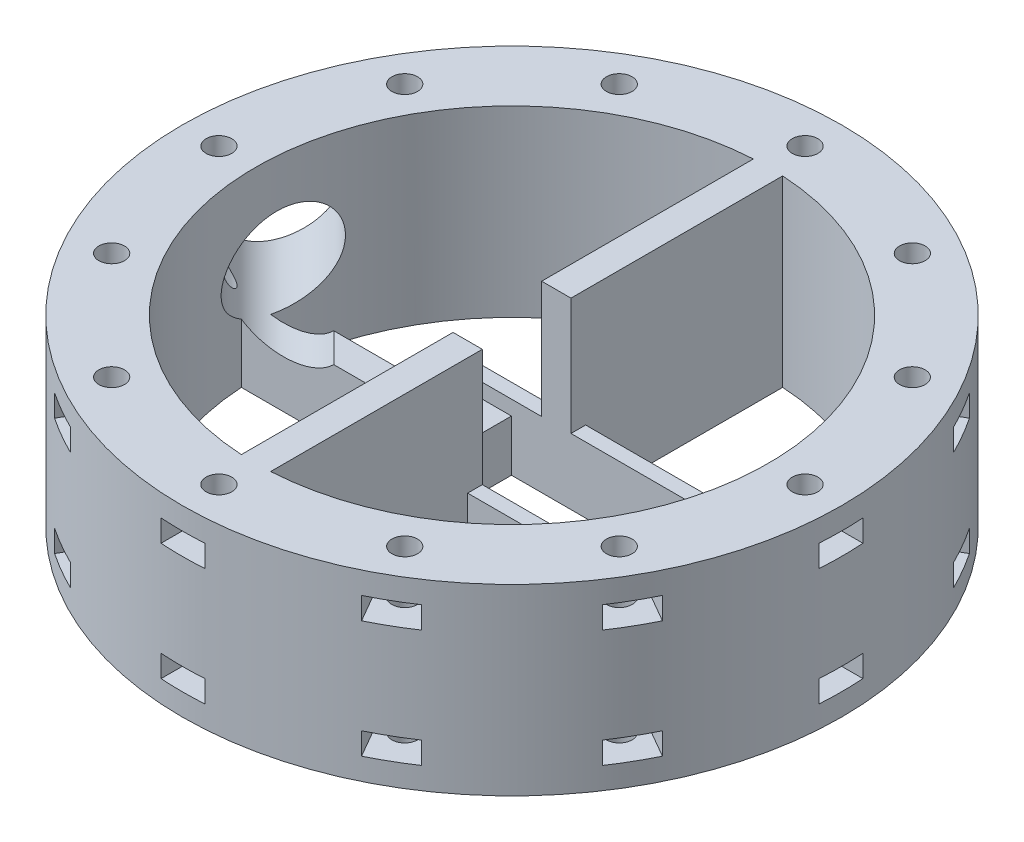
SolidWorks part; units mm, degrees
ref_plane "Front Plane" through (0, 0, 0) normal (0, 0, 1) x (1, 0, 0)
ref_plane "Top Plane" through (0, 0, 0) normal (0, 1, 0) x (1, 0, 0)
ref_plane "Right Plane" through (0, 0, 0) normal (1, 0, 0) x (0, 0, -1)
sketch "Sketch2" plane through (0, 0, 0) normal (0, 1, 0) x (1, 0, 0)
  line L0 (0, 0) -> (0, 45) construction
  circle A0 centre (0, 0) radius 45
  dimension "D1" = 90
extrude "Boss-Extrude1" add sketch "Sketch2" along normal blind 9
sketch "Sketch3" plane through (0, 9, 0) normal (0, 1, 0) x (1, 0, 0)
  line L0 (0, 45) -> (0, 0) construction
  line L1 (0, 0) -> (45, 0) construction
  line L2 (-10.95, 6.05) -> (21.3, 6.05)
  line L3 (21.3, 6.05) -> (21.3, -6.05)
  line L4 (-10.95, 6.05) -> (-10.95, -6.05)
  line L5 (-10.95, -6.05) -> (21.3, -6.05)
  circle A0 centre (0, 0) radius 45 construction
  point P12 (21.3, 0)
  point P13 (-10.95, 0)
  dimension "D1" = 32.25
  dimension "D2" = 10.95
  dimension "D3" = 12.1
extrude "Cut-Extrude1" cut sketch "Sketch3" against normal blind 2
sketch "Sketch4" plane through (0, 7, 0) normal (0, 1, 0) x (1, 0, 0)
  line L0 (5.175, 6.05) -> (5.175, -6.05) construction
  line L1 (21.3, 6.05) -> (-10.95, 6.05) construction
  line L2 (-10.95, -6.05) -> (21.3, -6.05) construction
  line L4 (-6.125, 6.05) -> (16.475, 6.05)
  line L5 (-6.125, 6.05) -> (-6.125, -6.05)
  line L6 (-6.125, -6.05) -> (16.475, -6.05)
  line L7 (16.475, 6.05) -> (16.475, -6.05)
  line L8 (-6.125, 6.05) -> (16.475, -6.05) construction
  line L9 (-6.125, -6.05) -> (16.475, 6.05) construction
  point P6 (5.175, 0)
  dimension "D1" = 22.6
extrude "Cut-Extrude2" cut sketch "Sketch4" against normal through all
sketch "Sketch6" plane through (0, 7, 0) normal (0, 1, 0) x (1, 0, 0)
  line L0 (-10.95, 0) -> (21.3, 0) construction
  line L1 (-10.95, 6.05) -> (-10.95, -6.05) construction
  line L2 (21.3, -6.05) -> (21.3, 6.05) construction
  line L3 (5.175, 6.05) -> (5.175, -6.05) construction
  line L4 (21.3, 6.05) -> (-10.95, 6.05) construction
  line L5 (-10.95, -6.05) -> (21.3, -6.05) construction
  circle A0 centre (-8.675, 0) radius 1
  circle A1 centre (19.025, 0) radius 1
  dimension "D1" = 2
  dimension "D2" = 27.7
extrude "Cut-Extrude4" cut sketch "Sketch6" against normal through all
sketch "Sketch9" plane through (0, 9, 0) normal (0, 1, 0) x (1, 0, 0)
  line L0 (-10.95, 6.05) -> (-10.95, -6.05) construction
  line L1 (-12.95, 8.05) -> (-2, 8.05)
  line L2 (-12.95, 8.05) -> (-12.95, 2)
  line L3 (-12.95, -8.05) -> (-2, -8.05)
  line L4 (-12.95, 2) -> (-34.9428, 2)
  line L6 (21.3, 6.05) -> (-10.95, 6.05) construction
  line L7 (0, 0) -> (-31.825, 0) construction
  line L8 (0, 0) -> (0, 31.7606) construction
  line L9 (-2, 34.9428) -> (-2, 8.05)
  line L10 (2, 34.9428) -> (2, 8.05)
  line L11 (-12.95, -2) -> (-34.9428, -2)
  line L12 (2, -34.9428) -> (2, -8.05)
  line L13 (-2, -34.9428) -> (-2, -8.05)
  line L14 (-12.95, -2) -> (-12.95, -8.05)
  line L15 (2, 8.05) -> (34.0617, 8.05)
  line L16 (2, -8.05) -> (34.0617, -8.05)
  arc A0 (34.0617, 8.05) -> (2, 34.9428) centre (0, 0) ccw
  arc A1 (-34.9428, -2) -> (-2, -34.9428) centre (0, 0) ccw
  arc A2 (-2, 34.9428) -> (-34.9428, 2) centre (0, 0) ccw
  arc A3 (2, -34.9428) -> (34.0617, -8.05) centre (0, 0) ccw
  dimension "D1" = 70
  dimension "D2" = 2
  dimension "D4" = 2
  dimension "D5" = 4
  dimension "D6" = 4
extrude "Cut-Extrude5" cut sketch "Sketch9" against normal through all
sketch "Sketch10" plane through (0, 0, 0) normal (0, -1, 0) x (1, 0, 0)
  circle A0 centre (0, 0) radius 40 construction
  circle A1 centre (-40, 0) radius 1.75
  circle A2 centre (-34.641, 20) radius 1.75
  circle A3 centre (-20, 34.641) radius 1.75
  circle A4 centre (0, 40) radius 1.75
  circle A5 centre (20, 34.641) radius 1.75
  circle A6 centre (34.641, 20) radius 1.75
  circle A7 centre (40, 0) radius 1.75
  circle A8 centre (34.641, -20) radius 1.75
  circle A9 centre (20, -34.641) radius 1.75
  circle A10 centre (0, -40) radius 1.75
  circle A11 centre (-20, -34.641) radius 1.75
  circle A12 centre (-34.641, -20) radius 1.75
  point P29 (0, 0)
  dimension "D1" = 80
  dimension "D2" = 3.5
  dimension "D3" = 12
sketch "Sketch13" plane through (0, 9, 0) normal (0, 1, 0) x (1, 0, 0)
  line L0 (2, -34.9428) -> (2, -8.05)
  line L1 (2, 6.05) -> (2, 34.9428)
  line L2 (-2, -8.05) -> (-2, -34.9428)
  line L3 (2, 6.05) -> (-2, 6.05)
  line L5 (2, -6.05) -> (-2, -6.05)
  line L6 (-2, 34.9428) -> (-2, 6.05)
  line L8 (2, -8.05) -> (2, -6.05)
  line L9 (-2, -6.05) -> (-2, -8.05)
  circle A0 centre (0, 0) radius 45
  arc A1 (34.9857, 1) -> (2, 34.9428) centre (0, 0) ccw
  arc A2 (-2, 34.9428) -> (-34.9428, 2) centre (0, 0) ccw
  arc A3 (-34.9428, 2) -> (-2, -34.9428) centre (0, 0) ccw
  arc A4 (2, -34.9428) -> (34.9857, 1) centre (0, 0) ccw
  dimension "D1" = 90
extrude "Boss-Extrude2" add sketch "Sketch13" along normal blind 16
extrude "Cut-Extrude7" cut sketch "Sketch10" against normal through all
ref_plane "Plane1" through (0, 22, 0) normal (0, 1, 0) x (1, 0, 0)
sketch "Sketch14" plane through (0, 22, 0) normal (0, 1, 0) x (1, 0, 0)
  line L0 (31.641, -18.2679) -> (31.641, -21.7321)
  line L1 (36.5359, 0) -> (38.2679, -3)
  line L2 (38.2679, -3) -> (44.8999, -3)
  line L3 (34.641, -16.5359) -> (31.641, -18.2679)
  line L4 (40.3844, -19.8519) -> (34.641, -16.5359)
  line L5 (44.8999, 3) -> (38.2679, 3)
  line L6 (38.2679, 3) -> (36.5359, 0)
  line L7 (43.4641, 0) -> (42.5981, 1.5) [skipped]
  line L8 (41.7321, -3) -> (42.5981, -1.5) [skipped]
  line L9 (31.641, -21.7321) -> (37.3844, -25.048)
  line L10 (18.2679, -31.641) -> (16.5359, -34.641)
  line L11 (21.7321, -31.641) -> (18.2679, -31.641)
  line L12 (25.048, -37.3844) -> (21.7321, -31.641)
  line L13 (16.5359, -34.641) -> (19.8519, -40.3844)
  line L14 (0, -36.5359) -> (-3, -38.2679)
  line L15 (3, -38.2679) -> (0, -36.5359)
  line L16 (3, -44.8999) -> (3, -38.2679)
  line L17 (-3, -38.2679) -> (-3, -44.8999)
  line L18 (-18.2679, -31.641) -> (-21.7321, -31.641)
  line L19 (-16.5359, -34.641) -> (-18.2679, -31.641)
  line L20 (-19.8519, -40.3844) -> (-16.5359, -34.641)
  line L21 (-21.7321, -31.641) -> (-25.048, -37.3844)
  line L22 (-31.641, -18.2679) -> (-34.641, -16.5359)
  line L23 (-31.641, -21.7321) -> (-31.641, -18.2679)
  line L24 (-37.3844, -25.048) -> (-31.641, -21.7321)
  line L25 (-34.641, -16.5359) -> (-40.3844, -19.8519)
  line L26 (-36.5359, 0) -> (-38.2679, 3)
  line L27 (-38.2679, -3) -> (-36.5359, 0)
  line L28 (-44.8999, -3) -> (-38.2679, -3)
  line L29 (-38.2679, 3) -> (-44.8999, 3)
  line L30 (-31.641, 18.2679) -> (-31.641, 21.7321)
  line L31 (-34.641, 16.5359) -> (-31.641, 18.2679)
  line L32 (-40.3844, 19.8519) -> (-34.641, 16.5359)
  line L33 (-31.641, 21.7321) -> (-37.3844, 25.048)
  line L34 (-18.2679, 31.641) -> (-16.5359, 34.641)
  line L35 (-21.7321, 31.641) -> (-18.2679, 31.641)
  line L36 (-25.048, 37.3844) -> (-21.7321, 31.641)
  line L37 (-16.5359, 34.641) -> (-19.8519, 40.3844)
  line L38 (0, 36.5359) -> (3, 38.2679)
  line L39 (-3, 38.2679) -> (0, 36.5359)
  line L40 (-3, 44.8999) -> (-3, 38.2679)
  line L41 (3, 38.2679) -> (3, 44.8999)
  line L42 (18.2679, 31.641) -> (21.7321, 31.641)
  line L43 (16.5359, 34.641) -> (18.2679, 31.641)
  line L44 (19.8519, 40.3844) -> (16.5359, 34.641)
  line L45 (21.7321, 31.641) -> (25.048, 37.3844)
  line L46 (31.641, 18.2679) -> (34.641, 16.5359)
  line L47 (31.641, 21.7321) -> (31.641, 18.2679)
  line L48 (37.3844, 25.048) -> (31.641, 21.7321)
  line L49 (34.641, 16.5359) -> (40.3844, 19.8519)
  circle A0 centre (40, 0) radius 3 construction
  arc A1 (44.8999, -3) -> (44.8999, 3) centre (0, 0) ccw
  arc A2 (37.3844, -25.048) -> (40.3844, -19.8519) centre (0, 0) ccw
  arc A3 (19.8519, -40.3844) -> (25.048, -37.3844) centre (0, 0) ccw
  arc A4 (-3, -44.8999) -> (3, -44.8999) centre (0, 0) ccw
  arc A5 (-25.048, -37.3844) -> (-19.8519, -40.3844) centre (0, 0) ccw
  arc A6 (-40.3844, -19.8519) -> (-37.3844, -25.048) centre (0, 0) ccw
  arc A7 (-44.8999, 3) -> (-44.8999, -3) centre (0, 0) ccw
  arc A8 (-37.3844, 25.048) -> (-40.3844, 19.8519) centre (0, 0) ccw
  arc A9 (-19.8519, 40.3844) -> (-25.048, 37.3844) centre (0, 0) ccw
  arc A10 (3, 44.8999) -> (-3, 44.8999) centre (0, 0) ccw
  arc A11 (25.048, 37.3844) -> (19.8519, 40.3844) centre (0, 0) ccw
  arc A12 (40.3844, 19.8519) -> (37.3844, 25.048) centre (0, 0) ccw
  point P71 (0, 0)
  dimension "D1" = 6
  dimension "D2" = 12
extrude "Cut-Extrude8" cut sketch "Sketch14" against normal blind 3
ref_plane "Plane2" through (0, 12.5, 0) normal (0, 1, 0) x (1, 0, 0)
mirror "Mirror1" about plane through (0, 12.5, 0) normal (0, 1, 0) of "Cut-Extrude8"
ref_plane "Plane3" through (0, 0, 0) normal (-0.7071, 0, -0.7071) x (-0.7071, 0, 0.7071)
sketch "Sketch15" plane through (0, 0, 0) normal (-0.7071, 0, -0.7071) x (-0.7071, 0, 0.7071)
  line L1 (14.5187, 19) -> (29.6277, 19) construction
  line L2 (14.5187, 6) -> (29.6277, 6) construction
  line L3 (22.0732, 19) -> (22.0732, 6) construction
  circle A0 centre (22.0732, 12.5) radius 6
  dimension "D1" = 12
extrude "Cut-Extrude9" cut sketch "Sketch15" along normal through all
